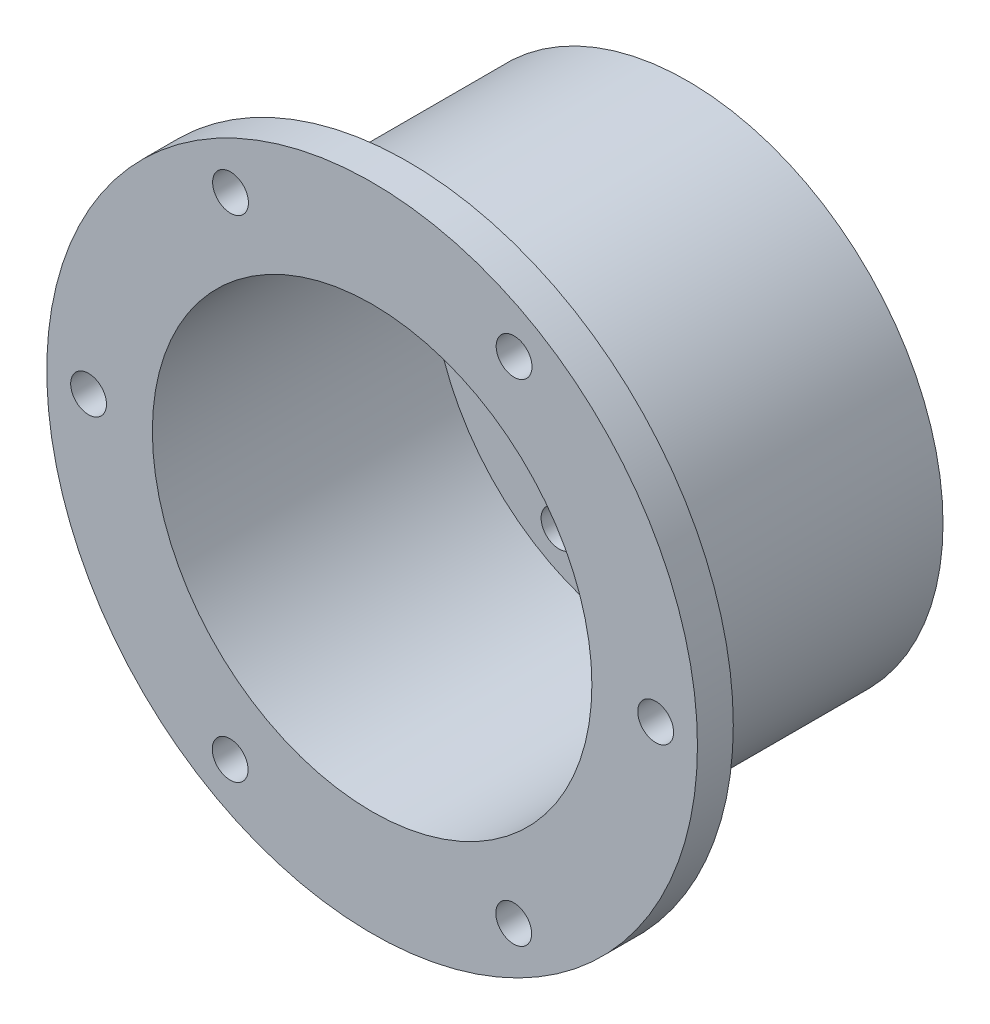
SolidWorks part; units mm, degrees
material "Resina de melamina"
ref_plane "Alzado" through (0, 0, 0) normal (0, 0, 1) x (1, 0, 0)
ref_plane "Planta" through (0, 0, 0) normal (0, 1, 0) x (1, 0, 0)
ref_plane "Vista lateral" through (0, 0, 0) normal (1, 0, 0) x (0, 0, -1)
sketch "Croquis1" plane through (0, 0, 0) normal (0, 0, 1) x (1, 0, 0)
  circle A0 centre (0, 0) radius 18.4
  circle A1 centre (0, 0) radius 21.4
  dimension "D1" = 36.8
  dimension "D2" = 42.8
extrude "Saliente-Extruir1" add sketch "Croquis1" along normal blind 26.4
sketch "Croquis2" plane through (0, 0, 0) normal (0, 0, -1) x (-1, 0, 0)
  circle A0 centre (0, 0) radius 18.65
  dimension "D1" = 37.3
extrude "Saliente-Extruir2" add sketch "Croquis2" against normal blind 3
sketch "Croquis3" plane through (0, 0, 26.4) normal (0, 0, 1) x (1, 0, 0)
  circle A0 centre (0, 0) radius 21.4
  circle A1 centre (0, 0) radius 27.24
  dimension "D1" = 54.48
extrude "Saliente-Extruir3" add sketch "Croquis3" against normal blind 3
sketch "Croquis4" plane through (0, 0, 0) normal (0, 0, -1) x (-1, 0, 0)
  line L0 (0, 0) -> (0, -7) construction
  line L1 (-13, 0) -> (-14, 0) construction
  line L2 (-14, 0) -> (-17, 0) construction
  circle A0 centre (0, -7) radius 6
  circle A9 centre (-15.5, 0) radius 1.5
  circle A10 centre (-7.75, 13.4234) radius 1.5
  circle A11 centre (7.75, 13.4234) radius 1.5
  circle A12 centre (15.5, 0) radius 1.5
  circle A13 centre (7.75, -13.4234) radius 1.5
  circle A14 centre (-7.75, -13.4234) radius 1.5
  dimension "D2" = 12
  dimension "D1" = 7
  dimension "D3" = 1
  dimension "D4" = 3
  dimension "D5" = 6
extrude "Cortar-Extruir1" cut sketch "Croquis4" against normal blind 3
sketch "Croquis6" plane through (0, 0, 26.4) normal (0, 0, 1) x (1, 0, 0)
  line L0 (0, 0) -> (-7.75, 13.4234) construction
  line L1 (-7.75, 13.4234) -> (-9.1877, 15.942) construction
  line L2 (-9.1877, 15.942) -> (-13.6018, 23.601) construction
  line L3 (-13.6018, 23.601) -> (-11.8541, 20.5686) construction
  circle A0 centre (0, 0) radius 18.4 construction
  circle A9 centre (0, 0) radius 27.24 construction
  circle A10 centre (-11.8541, 20.5686) radius 1.5
  circle A11 centre (11.8859, 20.5503) radius 1.5
  circle A12 centre (23.74, -0.0183) radius 1.5
  circle A13 centre (11.8541, -20.5686) radius 1.5
  circle A14 centre (-11.8859, -20.5503) radius 1.5
  circle A15 centre (-23.74, 0.0183) radius 1.5
  dimension "D1" = 3.5
  dimension "D2" = 3
  dimension "D3" = 6
extrude "Cortar-Extruir2" cut sketch "Croquis6" against normal blind 3
